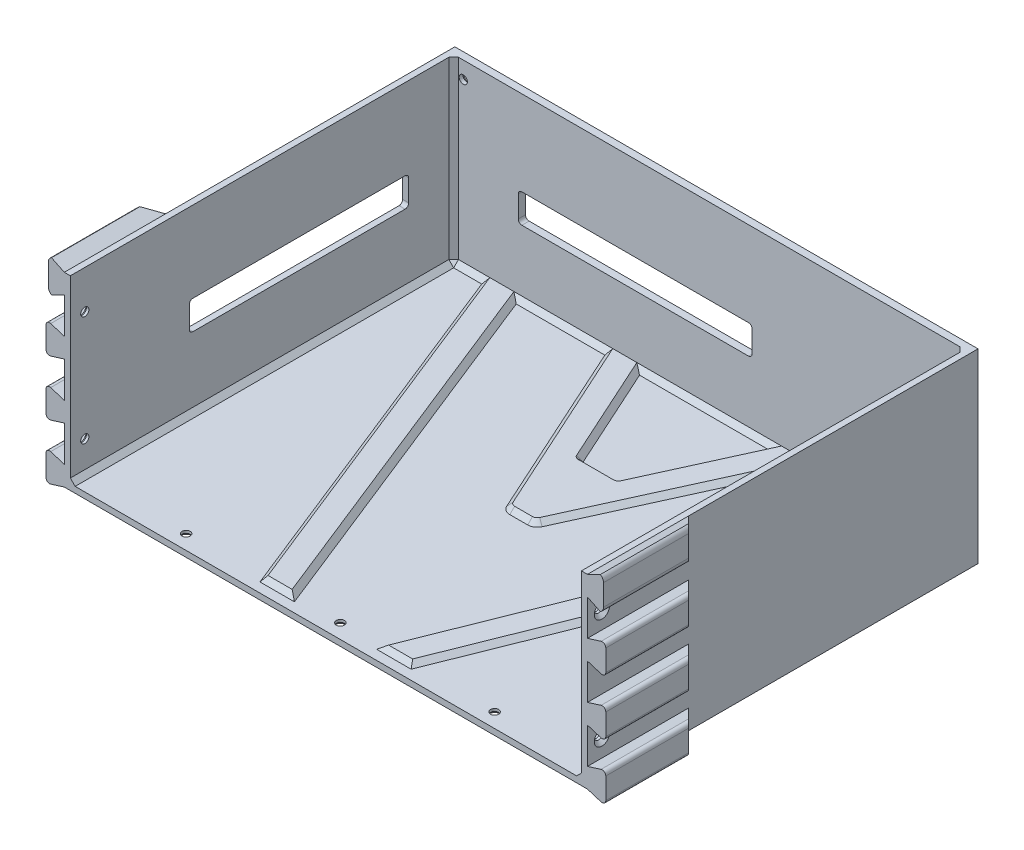
SolidWorks part; units mm, degrees
ref_plane "Płaszczyzna przednia" through (0, 0, 0) normal (0, 0, 1) x (1, 0, 0)
ref_plane "Płaszczyzna górna" through (0, 0, 0) normal (0, 1, 0) x (1, 0, 0)
ref_plane "Płaszczyzna prawa" through (0, 0, 0) normal (1, 0, 0) x (0, 0, -1)
sketch "Szkic1" plane through (0, 0, 0) normal (0, 0, 1) x (1, 0, 0)
  line L1 (0, 0) -> (217, 0)
  line L2 (0, 0) -> (0, 77.16)
  line L3 (0, 77.16) -> (217, 77.16)
  line L4 (217, 0) -> (217, 77.16)
  dimension "D1" = 77.16
  dimension "D2" = 217
extrude "Dodanie-wyciągnięcie1" add sketch "Szkic1" along normal blind 3
sketch "Szkic2" plane through (0, 0, 3) normal (0, 0, 1) x (1, 0, 0)
  line L0 (0, 77.16) -> (0, 0)
  line L1 (0, 0) -> (217, 0)
  line L2 (217, 0) -> (217, 77.16)
  line L3 (217, 77.16) -> (214.5, 77.16)
  line L4 (217, 77.16) -> (0, 77.16) construction
  line L5 (214.5, 77.16) -> (214.5, 2.5)
  line L6 (214.5, 2.5) -> (2.5, 2.5)
  line L7 (2.5, 2.5) -> (2.5, 77.16)
  line L8 (2.5, 77.16) -> (0, 77.16)
  dimension "D1" = 2.5
  dimension "D2" = 2.5
  dimension "D3" = 2.5
extrude "Dodanie-wyciągnięcie2" add sketch "Szkic2" along normal blind 159
sketch "Szkic3" plane through (0, 2.5, 0) normal (0, 1, 0) x (1, 0, 0)
  line L0 (17.5, -3) -> (78.5, -156)
  line L1 (214.5, -3) -> (2.5, -3) construction
  line L3 (27.5, -3) -> (88.5, -156)
  line L4 (214.5, -3) -> (2.5, -3) construction
  line L5 (101.1515, -50) -> (115.8485, -50)
  line L6 (78.5, -156) -> (88.5, -156)
  line L7 (17.5, -3) -> (27.5, -3)
  line L8 (199.5, -3) -> (138.5, -156)
  line L9 (138.5, -156) -> (128.5, -156)
  line L10 (128.5, -156) -> (138.5, -156)
  line L11 (128.5, -156) -> (189.5, -3)
  line L12 (189.5, -3) -> (199.5, -3)
  line L13 (217, 0) -> (0, 0) construction
  line L14 (68.5, -3) -> (102.9671, -78.8276)
  line L15 (114.0329, -78.8276) -> (148.5, -3)
  line L16 (138.5, -3) -> (117.6693, -48.8276)
  line L17 (99.3307, -48.8276) -> (78.5, -3)
  line L18 (104.7878, -80) -> (112.2122, -80)
  line L19 (68.5, -3) -> (78.5, -3)
  line L20 (138.5, -3) -> (148.5, -3)
  line L21 (108.5, 0) -> (108.5, -100) construction
  line L23 (214.5, -162) -> (2.5, -162) construction
  arc A0 (115.8485, -50) -> (117.6693, -48.8276) centre (115.8485, -48) ccw
  arc A1 (101.1515, -50) -> (99.3307, -48.8276) centre (101.1515, -48) cw
  arc A2 (112.2122, -80) -> (114.0329, -78.8276) centre (112.2122, -78) ccw
  arc A3 (104.7878, -80) -> (102.9671, -78.8276) centre (104.7878, -78) cw
  point P14 (108.5, 0)
  point P33 (113.5, -80)
  point P36 (103.5, -80)
  point P39 (108.5, -50)
  line M5 (214.5, -3) -> (2.5, -3)
  line M7 (2.5, -162) -> (214.5, -162)
  dimension "D16" = 2
  dimension "D1" = 20
  dimension "D2" = 15
  dimension "D3" = 40
  dimension "D4" = 10
  dimension "D5" = 15
  dimension "D6" = 10
  dimension "D7" = 10
  dimension "D8" = 10
  dimension "D9" = 10
  dimension "D10" = 10
  dimension "D11" = 10
  dimension "D12" = 5
  dimension "D13" = 60
  dimension "D14" = 80
  dimension "D15" = 30
  dimension "D17" = 6
extrude "Dodanie-wyciągnięcie3" add sketch "Szkic3" along normal blind 2 contours L3 L0 M5 M7 | L11 L8 M7 M5 | L20 L15 A2 L18 A3 L14 L19 L17 A1 L5 A0 L16 region at (53, 2.5, 79.5) region at (164, 2.5, 79.5)
chamfer "Sfazowanie2" distance 2 angle 45 25 edges at (169, 2.5, 79.5) (214.5, 39.83, 3) (214.5, 2.5, 82.5) (207, 2.5, 3) (58, 2.5, 79.5) (159, 2.5, 79.5) (169, 2.5, 3) (48, 2.5, 3) (48, 2.5, 79.5) (10, 2.5, 3) (2.5, 2.5, 82.5) (2.5, 39.83, 3) (108.5, 2.5, 3) (85.7335, 2.5, 40.9138) (103.7051, 2.5, 79.6815) (108.5, 2.5, 80) (113.2949, 2.5, 79.6815) (131.2665, 2.5, 40.9138) (128.0846, 2.5, 25.9138) (116.9313, 2.5, 49.6815) (108.5, 2.5, 50) (100.0687, 2.5, 49.6815) (88.9154, 2.5, 25.9138) (133.5, 2.5, 156) (83.5, 2.5, 156)
sketch "Szkic10" plane through (0, 0, 162) normal (0, 0, 1) x (1, 0, 0)
  line L0 (224.6, 87) -> (224.6, 0) construction
  line L1 (217, 0) -> (217, 77.16) construction
  line L2 (217, 0) -> (217, 8.16)
  line L3 (217, 0) -> (222.6526, -1.7665)
  line L4 (217, 8.16) -> (222.6526, 9.9265)
  line L5 (224.6, 8.4948) -> (224.6, -0.3348)
  line L6 (108.5, 77.16) -> (108.5, 114.4452) construction
  line L7 (212.5, 77.16) -> (4.5, 77.16) construction
  line L8 (217, 23) -> (217, 31.16)
  line L9 (217, 23) -> (222.6526, 21.2335)
  line L10 (217, 31.16) -> (222.6526, 32.9265)
  line L11 (224.6, 31.4948) -> (224.6, 22.6652)
  line L12 (217, 46) -> (217, 54.16)
  line L13 (217, 46) -> (222.6526, 44.2335)
  line L14 (217, 54.16) -> (222.6526, 55.9265)
  line L15 (224.6, 54.4948) -> (224.6, 45.6652)
  line L16 (-7.6, 54.4948) -> (-7.6, 45.6652)
  line L17 (0, 54.16) -> (-5.6526, 55.9265)
  line L18 (0, 46) -> (-5.6526, 44.2335)
  line L19 (0, 46) -> (0, 54.16)
  line L20 (-7.6, 31.4948) -> (-7.6, 22.6652)
  line L21 (0, 31.16) -> (-5.6526, 32.9265)
  line L22 (0, 23) -> (-5.6526, 21.2335)
  line L23 (0, 23) -> (0, 31.16)
  line L24 (-7.6, 8.4948) -> (-7.6, -0.3348)
  line L25 (0, 8.16) -> (-5.6526, 9.9265)
  line L26 (0, 0) -> (-5.6526, -1.7665)
  line L27 (0, 0) -> (0, 8.16)
  line L28 (217, 69) -> (217, 77.16)
  line L29 (217, 69) -> (222.3314, 66.4215)
  line L30 (217, 77.16) -> (222.3314, 79.7385)
  line L31 (223.6594, 77.4948) -> (223.6594, 68.6652)
  line L32 (-6.6594, 77.4948) -> (-6.6594, 68.6652)
  line L33 (0, 77.16) -> (-5.3314, 79.7385)
  line L34 (0, 69) -> (-5.3314, 66.4215)
  line L35 (0, 69) -> (0, 77.16)
  arc A0 (222.6526, -1.7665) -> (224.6, -0.3348) centre (223.1, -0.3348) ccw
  arc A1 (222.6526, 9.9265) -> (224.6, 8.4948) centre (223.1, 8.4948) cw
  arc A2 (222.6526, 21.2335) -> (224.6, 22.6652) centre (223.1, 22.6652) ccw
  arc A3 (222.6526, 32.9265) -> (224.6, 31.4948) centre (223.1, 31.4948) cw
  arc A4 (222.6526, 44.2335) -> (224.6, 45.6652) centre (223.1, 45.6652) ccw
  arc A5 (222.6526, 55.9265) -> (224.6, 54.4948) centre (223.1, 54.4948) cw
  arc A6 (-5.6526, 55.9265) -> (-7.6, 54.4948) centre (-6.1, 54.4948) ccw
  arc A7 (-5.6526, 44.2335) -> (-7.6, 45.6652) centre (-6.1, 45.6652) cw
  arc A8 (-5.6526, 32.9265) -> (-7.6, 31.4948) centre (-6.1, 31.4948) ccw
  arc A9 (-5.6526, 21.2335) -> (-7.6, 22.6652) centre (-6.1, 22.6652) cw
  arc A10 (-5.6526, 9.9265) -> (-7.6, 8.4948) centre (-6.1, 8.4948) ccw
  arc A11 (-5.6526, -1.7665) -> (-7.6, -0.3348) centre (-6.1, -0.3348) cw
  arc A12 (222.3314, 66.4215) -> (223.6594, 68.6652) centre (221.1, 68.6652) ccw
  arc A13 (222.3314, 79.7385) -> (223.6594, 77.4948) centre (221.1, 77.4948) cw
  arc A14 (-5.3314, 79.7385) -> (-6.6594, 77.4948) centre (-4.1, 77.4948) ccw
  arc A15 (-5.3314, 66.4215) -> (-6.6594, 68.6652) centre (-4.1, 68.6652) cw
  point P11 (224.6, -2.3751)
  point P14 (224.6, 10.5351)
  point P60 (-7.6, 10.5351)
  point P61 (-7.6, -2.3751)
  dimension "D5" = 1.5
  dimension "D1" = 7.6
  dimension "D2" = 8.16
  dimension "D3" = 23
  dimension "D4" = 34.71
  dimension "D6" = 3
extrude "Dodanie-wyciągnięcie6" add sketch "Szkic10" against normal blind 32
chamfer "Sfazowanie5" distance 10 angle 45 8 edges at (217, 50.08, 130) (217, 4.08, 130) (0, 4.08, 130) (0, 27.08, 130) (0, 50.08, 130) (217, 27.08, 130) (217, 73.08, 130) (0, 73.08, 130)
ref_plane "Płaszczyzna1" through (108.5, 0, 0) normal (-1, 0, 0) x (0, 0, 1)
sketch "Sketch1" plane through (0, 0, 0) normal (-1, 0, 0) x (0, 0, 1)
  line L4 (21.6472, 42.16) -> (21.6472, 33.16)
  line L5 (23.1472, 31.66) -> (111.1472, 31.66)
  line L6 (112.6472, 33.16) -> (112.6472, 42.16)
  line L7 (111.1472, 43.66) -> (23.1472, 43.66)
  line L8 (21.6472, 42.16) -> (21.6472, 33.16)
  line L9 (23.1472, 31.66) -> (111.1472, 31.66)
  line L10 (112.6472, 33.16) -> (112.6472, 42.16)
  line L11 (111.1472, 43.66) -> (23.1472, 43.66)
  arc A4 (23.1472, 43.66) -> (21.6472, 42.16) centre (23.1472, 42.16) ccw
  arc A5 (21.6472, 33.16) -> (23.1472, 31.66) centre (23.1472, 33.16) ccw
  arc A6 (111.1472, 31.66) -> (112.6472, 33.16) centre (111.1472, 33.16) ccw
  arc A7 (112.6472, 42.16) -> (111.1472, 43.66) centre (111.1472, 42.16) ccw
  arc A8 (23.1472, 43.66) -> (21.6472, 42.16) centre (23.1472, 42.16) ccw
  arc A9 (21.6472, 33.16) -> (23.1472, 31.66) centre (23.1472, 33.16) ccw
  arc A10 (111.1472, 31.66) -> (112.6472, 33.16) centre (111.1472, 33.16) ccw
  arc A11 (112.6472, 42.16) -> (111.1472, 43.66) centre (111.1472, 42.16) ccw
  dimension "D1" = 0
extrude "Cut-Extrude1" cut sketch "Sketch1" against normal up to next contours L9 A10 L10 A11 L11 A8 L8 A9
sketch "Sketch2" plane through (0, 0, 0) normal (0, 0, -1) x (-1, 0, 0)
  line L4 (-124.7972, 29.96) -> (-30.7972, 29.96)
  line L5 (-29.2972, 31.46) -> (-29.2972, 40.46)
  line L6 (-30.7972, 41.96) -> (-124.7972, 41.96)
  line L7 (-126.2972, 40.46) -> (-126.2972, 31.46)
  line L8 (-124.7972, 29.96) -> (-30.7972, 29.96)
  line L9 (-29.2972, 31.46) -> (-29.2972, 40.46)
  line L10 (-30.7972, 41.96) -> (-124.7972, 41.96)
  line L11 (-126.2972, 40.46) -> (-126.2972, 31.46)
  arc A4 (-126.2972, 31.46) -> (-124.7972, 29.96) centre (-124.7972, 31.46) ccw
  arc A5 (-30.7972, 29.96) -> (-29.2972, 31.46) centre (-30.7972, 31.46) ccw
  arc A6 (-29.2972, 40.46) -> (-30.7972, 41.96) centre (-30.7972, 40.46) ccw
  arc A7 (-124.7972, 41.96) -> (-126.2972, 40.46) centre (-124.7972, 40.46) ccw
  arc A8 (-126.2972, 31.46) -> (-124.7972, 29.96) centre (-124.7972, 31.46) ccw
  arc A9 (-30.7972, 29.96) -> (-29.2972, 31.46) centre (-30.7972, 31.46) ccw
  arc A10 (-29.2972, 40.46) -> (-30.7972, 41.96) centre (-30.7972, 40.46) ccw
  arc A11 (-124.7972, 41.96) -> (-126.2972, 40.46) centre (-124.7972, 40.46) ccw
  dimension "D1" = 0
extrude "Cut-Extrude2" cut sketch "Sketch2" against normal up to next contours L10 A11 L11 A8 L8 A9 L9 A10
sketch "Sketch3" plane through (217, 0, 0) normal (1, 0, 0) x (0, 0, -1)
  circle A0 centre (-156, 61.2082) radius 2 construction
  circle A1 centre (-156, 15.58) radius 2 construction
  circle A2 centre (-156, 61.2082) radius 2
  circle A3 centre (-156, 15.58) radius 2
sketch "Sketch4" plane through (0, 0, 0) normal (0, -1, 0) x (1, 0, 0)
  circle A0 centre (44.5, 156) radius 2 construction
  circle A1 centre (108.5, 156) radius 2 construction
  circle A2 centre (172.5, 156) radius 2 construction
  circle A3 centre (44.5, 156) radius 2
  circle A4 centre (108.5, 156) radius 2
  circle A5 centre (172.5, 156) radius 2
sketch "Sketch5" plane through (0, 0, 0) normal (-1, 0, 0) x (0, 0, 1)
  circle A0 centre (156, 61.2082) radius 2 construction
  circle A1 centre (156, 15.58) radius 2 construction
  circle A2 centre (156, 61.2082) radius 2
  circle A3 centre (156, 15.58) radius 2
sketch "Sketch6" plane through (0, 0, 0) normal (-1, 0, 0) x (0, 0, 1)
  point P0 (156, 61.2082)
  point P3 (156, 15.58)
hole_wizard "CSK for M3 Countersunk Flat Head Screw1" positions "Sketch6" profile "Sketch7" countersink size "M3" standard "DIN" end condition up to next
sketch "Sketch7" plane through (0, 61.2082, 156) normal (0, 1, 0) x (0, 0, 1)
  line L0 (0, 0) -> (0, 2.5)
  line L1 (0, 2.5) -> (1.7, 2.5)
  line L2 (1.7, 2.5) -> (1.7, 1.45)
  line L3 (1.7, 1.45) -> (3.15, 0)
  line L5 (3.15, 0) -> (0, 0)
  line L6 (-1.7, 1.45) -> (-3.15, 0) construction
  line L11 (0, -6.35) -> (0, 107.95) construction
  dimension "Thru Hole Dia." = 3.4
  dimension "Thru Hole Depth" = 2.5
  dimension "Near C'Sink Dia." = 6.3
  dimension "Near C'Sink Angle" = 90
hole_wizard "CSK for M3 Countersunk Flat Head Screw2" positions "Sketch8" profile "Sketch9" countersink size "M3" standard "DIN" end condition up to next
sketch "Sketch8" plane through (0, 0, 0) normal (0, -1, 0) x (-1, 0, 0)
  point P0 (-44.5, -156)
  point P3 (-108.5, -156)
  point P6 (-172.5, -156)
sketch "Sketch9" plane through (44.5, 0, 156) normal (1, 0, 0) x (0, 0, -1)
  line L0 (0, 0) -> (0, 2.5)
  line L1 (0, 2.5) -> (1.7, 2.5)
  line L2 (1.7, 2.5) -> (1.7, 1.45)
  line L3 (1.7, 1.45) -> (3.15, 0)
  line L5 (3.15, 0) -> (0, 0)
  line L6 (-1.7, 1.45) -> (-3.15, 0) construction
  line L11 (0, -6.35) -> (0, 107.95) construction
  dimension "Thru Hole Dia." = 3.4
  dimension "Thru Hole Depth" = 2.5
  dimension "Near C'Sink Dia." = 6.3
  dimension "Near C'Sink Angle" = 90
sketch "Sketch10" plane through (217, 0, 0) normal (1, 0, 0) x (0, 0, -1)
  point P0 (-156, 61.2082)
  point P3 (-156, 15.58)
hole_wizard "CSK for M3 Countersunk Flat Head Screw3" positions "Sketch10" profile "Sketch11" countersink size "M3" standard "DIN" end condition up to next
sketch "Sketch11" plane through (217, 61.2082, 156) normal (0, 1, 0) x (0, 0, -1)
  line L0 (0, 0) -> (0, 2.5)
  line L1 (0, 2.5) -> (1.7, 2.5)
  line L2 (1.7, 2.5) -> (1.7, 1.45)
  line L3 (1.7, 1.45) -> (3.15, 0)
  line L5 (3.15, 0) -> (0, 0)
  line L6 (-1.7, 1.45) -> (-3.15, 0) construction
  line L11 (0, -6.35) -> (0, 107.95) construction
  dimension "Thru Hole Dia." = 3.4
  dimension "Thru Hole Depth" = 2.5
  dimension "Near C'Sink Dia." = 6.3
  dimension "Near C'Sink Angle" = 90
sketch "Sketch12" plane through (0, 0, 0) normal (0, 0, -1) x (-1, 0, 0)
  circle A0 centre (-210.5, 70.16) radius 2 construction
  circle A1 centre (-6.5, 70.16) radius 2 construction
  circle A2 centre (-210.5, 70.16) radius 2
  circle A3 centre (-6.5, 70.16) radius 2
sketch "Sketch14" plane through (0, 0, 0) normal (0, 0, -1) x (-1, 0, 0)
  point P0 (-210.5, 70.16)
  point P3 (-6.5, 70.16)
hole_wizard "CSK for M3 Countersunk Flat Head Screw4" positions "Sketch14" profile "Sketch15" countersink size "M3" standard "DIN" end condition up to next
sketch "Sketch15" plane through (210.5, 70.16, 0) normal (1, 0, 0) x (0, 1, 0)
  line L0 (0, 0) -> (0, 3)
  line L1 (0, 3) -> (1.7, 3)
  line L2 (1.7, 3) -> (1.7, 1.45)
  line L3 (1.7, 1.45) -> (3.15, 0)
  line L5 (3.15, 0) -> (0, 0)
  line L6 (-1.7, 1.45) -> (-3.15, 0) construction
  line L11 (0, -6.35) -> (0, 107.95) construction
  dimension "Thru Hole Dia." = 3.4
  dimension "Thru Hole Depth" = 3
  dimension "Near C'Sink Dia." = 6.3
  dimension "Near C'Sink Angle" = 90
